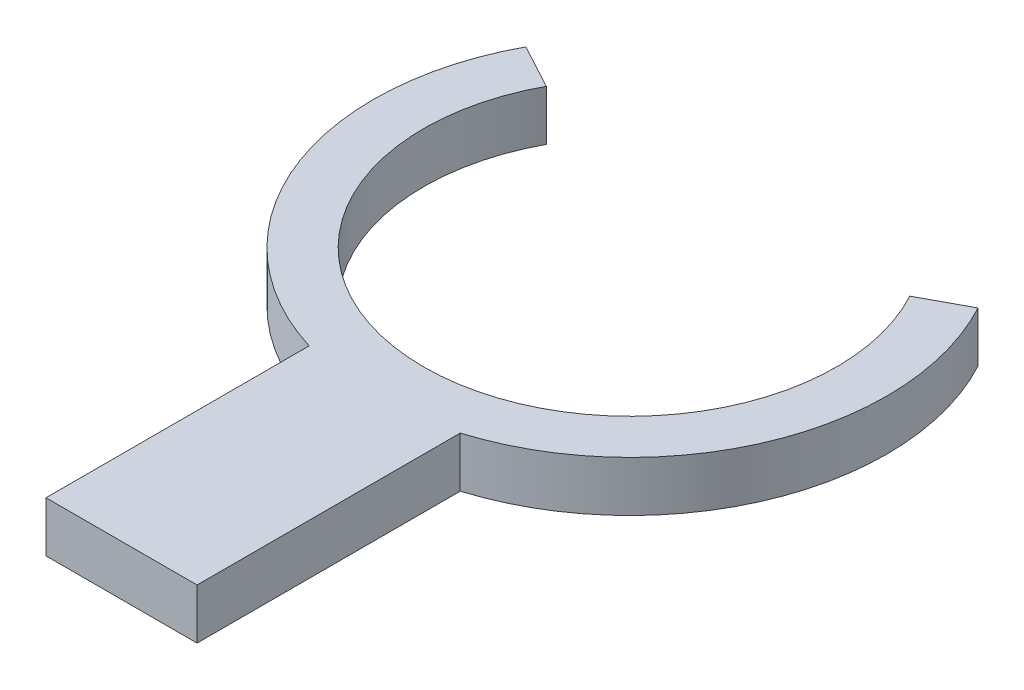
SolidWorks part; units mm, degrees
ref_plane "Front Plane" through (0, 0, 0) normal (0, 0, 1) x (1, 0, 0)
ref_plane "Top Plane" through (0, 0, 0) normal (0, 1, 0) x (1, 0, 0)
ref_plane "Right Plane" through (0, 0, 0) normal (1, 0, 0) x (0, 0, -1)
sketch "Sketch1" plane through (0, 0, 0) normal (0, 1, 0) x (1, 0, 0)
  line L0 (-51, 0) -> (-41, 0)
  line L1 (-41, 0) -> (41, 0)
  line L2 (41, 0) -> (51, 0)
  line L3 (0, 0) -> (0, -101) construction
  line L4 (-15, -101) -> (15, -101) construction
  line L5 (-15, -101) -> (15, -101)
  line L6 (-15, -101) -> (-14.9891, 0)
  line L7 (15, -101) -> (15.0109, 0)
  line L8 (-14.9891, 0) -> (15.0109, 0)
  line L9 (0, 0) -> (-44.8978, 24.1907)
  line L10 (0, 0) -> (44.8978, 24.1907)
  circle A0 centre (0, 0) radius 41
  circle A1 centre (0, 0) radius 51
  point P12 (0, -101)
  dimension "D1" = 82
  dimension "D2" = 102
  dimension "D3" = 101
  dimension "D4" = 30
extrude "Boss-Extrude1" add sketch "Sketch1" along normal blind 10 contours L9 A1 L0 A0 | L0 A1 L6 A0 | L6 A1 L7 A0 | A1 L6 L5 L7 | L7 A1 L2 A0 | L2 A1 L10 A0 region at (-44.3242, 0, -11.181) region at (-35.2532, 0, 25.1776) region at (0.0029, 0, 75.623) region at (0.0065, 0, 45.1476) region at (44.3242, 0, -11.181) region at (35.2579, 0, 25.1734)
